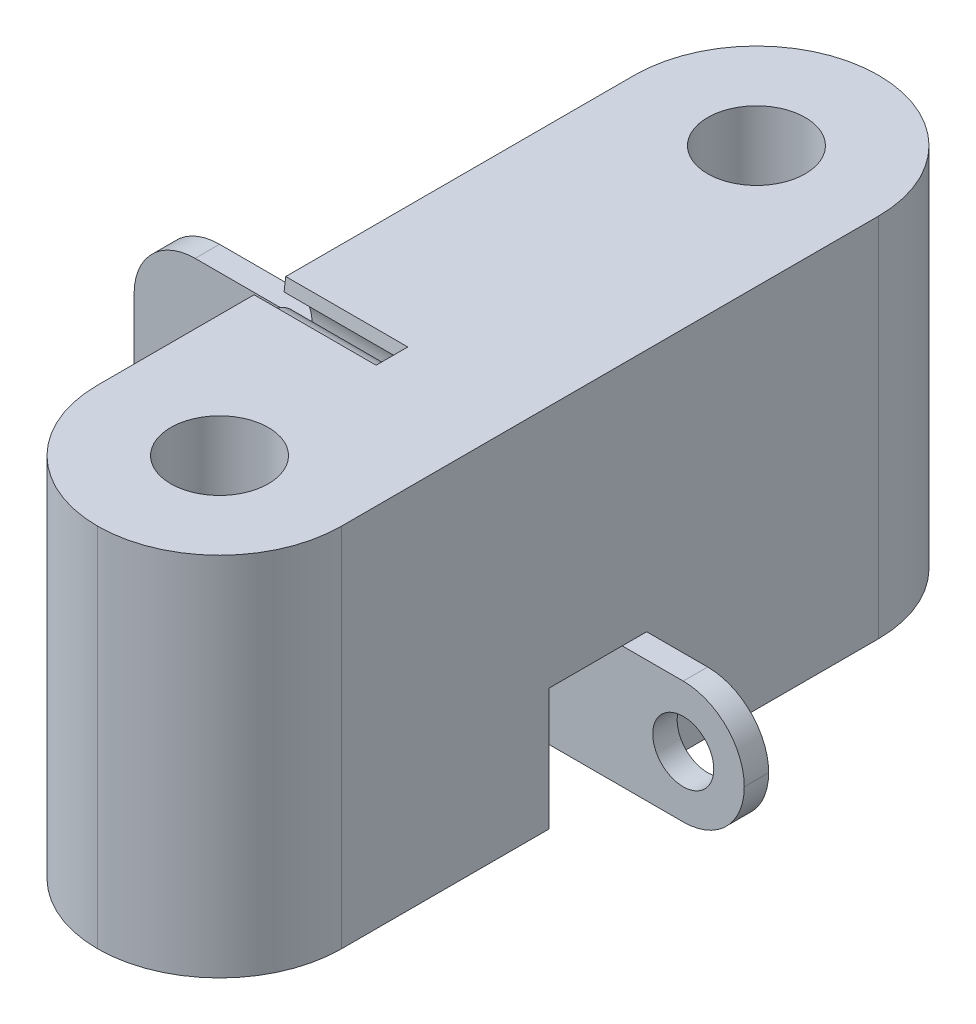
SolidWorks part; units mm, degrees
ref_plane "Front Plane" through (0, 0, 0) normal (0, 0, 1) x (1, 0, 0)
ref_plane "Top Plane" through (0, 0, 0) normal (0, 1, 0) x (1, 0, 0)
ref_plane "Right Plane" through (0, 0, 0) normal (1, 0, 0) x (0, 0, -1)
sketch "Sketch2" plane through (0, 0, 0) normal (0, 1, 0) x (1, 0, 0)
  line L1 (-3.5224, 23.7612) -> (16.4776, 23.7612)
  line L2 (-3.5224, 23.7612) -> (-3.5224, -40.2388)
  line L3 (-3.5224, -40.2388) -> (16.4776, -40.2388)
  line L4 (16.4776, 23.7612) -> (16.4776, -40.2388)
  dimension "D1" = 64
  dimension "D2" = 20
extrude "Boss-Extrude1" add sketch "Sketch2" along normal blind 30
sketch "Sketch3" plane through (0, 30, 0) normal (0, 1, 0) x (1, 0, 0)
  circle A0 centre (6.4776, 13.7612) radius 4
  circle A1 centre (6.4776, -30.2388) radius 4
  dimension "D13" = 8
  dimension "D14" = 8
extrude "Cut-Extrude1" cut sketch "Sketch3" against normal blind 20
sketch "Sketch4" plane through (-3.5224, 0, 0) normal (-1, 0, 0) x (0, 0, 1)
  line L0 (8.1636, 30.0512) -> (8.1636, 15.6029) construction
  line L1 (-23.743, 30.1264) -> (40.1453, 30.1264)
  line L2 (-23.743, 30.1264) -> (-23.743, 15.6782)
  line L3 (-23.743, 15.6782) -> (40.1453, 15.6782)
  line L4 (40.1453, 30.1264) -> (40.1453, 15.6782)
  line L5 (14.95, 28.9694) -> (14.7857, 30.2017)
  line L6 (14.7857, 30.2017) -> (17.4195, 30.2017)
  line L7 (17.4195, 30.2017) -> (17.3442, 28.9224)
  circle A0 centre (16.1636, 25.6866) radius 2.5
  circle A1 centre (16.1636, 25.6866) radius 3.5
  dimension "D2" = 5
  dimension "D3" = 7
  dimension "D1" = 8
extrude "Cut-Extrude2" cut sketch "Sketch4" against normal blind 10
fillet "Fillet1" radius 10 4 edges at (-3.5224, 15, -23.7612) (16.4776, 15, -23.7612) (16.4776, 15, 40.2388) (-3.5224, 15, 40.2388)
sketch "Sketch5" plane through (-3.5224, 0, 0) normal (-1, 0, 0) x (0, 0, 1)
  line L0 (-13.7612, 30) -> (14.8126, 30) construction
  line L1 (5.2388, 30) -> (7.2388, 30)
  line L2 (5.2388, 30) -> (5.2388, 0)
  line L3 (5.2388, 0) -> (7.2388, 0)
  line L4 (7.2388, 30) -> (7.2388, 0)
  line L5 (-13.7612, 30) -> (-13.7612, 0) construction
  dimension "D1" = 2
  dimension "D2" = 30
  dimension "D3" = 0
  dimension "D4" = 19
extrude "Boss-Extrude2" add sketch "Sketch5" along normal blind 20 and the other way blind 30
sketch "Sketch6" plane through (0, 0, 5.2388) normal (0, 0, -1) x (-1, 0, 0)
  line L0 (-26.4776, 30) -> (-16.4776, 30) construction
  line L1 (-26.4776, 30) -> (-16.4776, 30)
  line L2 (-26.4776, 30) -> (-26.4776, 10)
  line L3 (-26.4776, 10) -> (-16.4776, 10)
  line L4 (-16.4776, 30) -> (-16.4776, 10)
  line L5 (-26.4776, 30) -> (-26.4776, 0) construction
  line L6 (23.5224, 30) -> (23.5224, 0) construction
  line L7 (3.5224, 30) -> (23.5224, 30)
  line L8 (3.5224, 30) -> (3.5224, 20)
  line L9 (3.5224, 20) -> (23.5224, 20)
  line L10 (23.5224, 30) -> (23.5224, 20)
  line L11 (3.5224, 0) -> (23.5224, 0) construction
  circle A0 centre (-21.4776, 5) radius 2.5
  circle A1 centre (13.5224, 5) radius 2.5
  point P10 (-21.4776, 10)
  dimension "D5" = 5
  dimension "D10" = 5
  dimension "D1" = 20
  dimension "D2" = 10
  dimension "D3" = 0
  dimension "D4" = 0
  dimension "D6" = 5
  dimension "D7" = 5
  dimension "D8" = 10
  dimension "D9" = 20
  dimension "D11" = 10
  dimension "D12" = 15
  dimension "D13" = 5
  dimension "D14" = 0
  dimension "D15" = 35
extrude "Cut-Extrude3" cut sketch "Sketch6" against normal up to next
fillet "Fillet2" radius 5 4 edges at (-23.5224, 20, 6.2388) (-23.5224, 0, 6.2388) (26.4776, 0, 6.2388) (26.4776, 10, 6.2388)
sketch "Sketch7" plane through (0, 0, 0) normal (0, -1, 0) x (-1, 0, 0)
  line L0 (-21.4776, -7.2388) -> (-16.4776, -7.2388) construction
  line L1 (4.0224, -7.2388) -> (-16.9776, -7.2388)
  line L2 (4.0224, -7.2388) -> (4.0224, -13.2388)
  line L3 (4.0224, -13.2388) -> (-16.9776, -13.2388)
  line L4 (-16.9776, -7.2388) -> (-16.9776, -13.2388)
  line L5 (3.5224, -7.2388) -> (3.5224, -30.2388) construction
  dimension "D1" = 6
  dimension "D2" = 0
  dimension "D3" = 21
  dimension "D4" = 0.5
extrude "Cut-Extrude4" cut sketch "Sketch7" against normal blind 10
